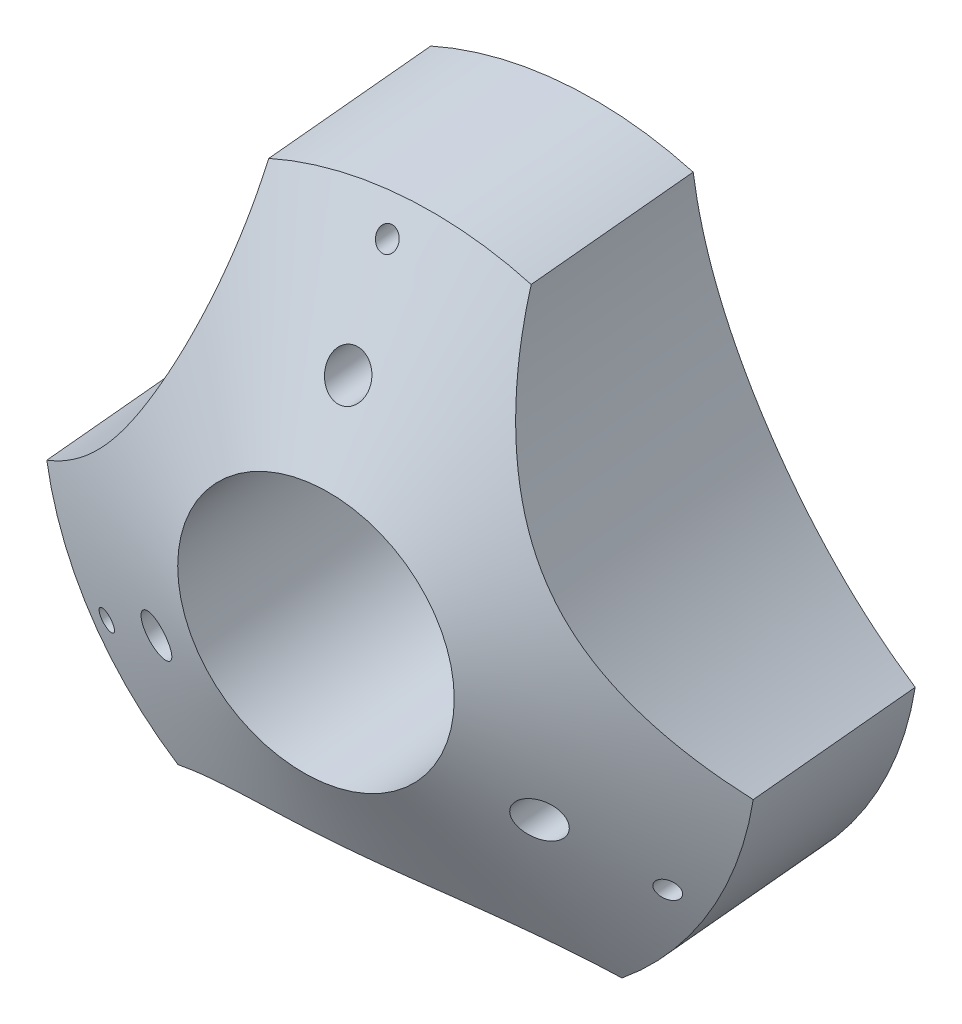
SolidWorks part; units mm, degrees
material "ABS"
ref_plane "前视基准面" through (0, 0, 0) normal (0, 0, 1) x (1, 0, 0)
ref_plane "上视基准面" through (0, 0, 0) normal (0, 1, 0) x (1, 0, 0)
ref_plane "右视基准面" through (0, 0, 0) normal (1, 0, 0) x (0, 0, -1)
other "Configuration Table"
sketch "草图1" plane through (0, 0, 0) normal (0, 1, 0) x (1, 0, 0)
  line L0 (0, 0) -> (50000, 0) construction
  line L1 (0, 0) -> (43301.2702, 25000) construction
  line L2 (0, 0) -> (25000, 43301.2702) construction
  line L3 (0, 0) -> (0, 50000) construction
  line L4 (0, 0) -> (-25000, 43301.2702) construction
  line L5 (0, 0) -> (-43301.2702, 25000) construction
  line L6 (-31.9455, 0) -> (-30.3426, -17.5183)
  line L7 (-30.3426, -17.5183) -> (-61.1307, -35.2938)
  line L8 (-61.1307, -35.2938) -> (-64.36, 0)
  line L9 (-64.36, 0) -> (-31.9455, 0)
  line L10 (-62.9002, -15.9548) -> (-52.9418, -15.0436) construction
  line L11 (-52.9418, -15.0436) -> (-54.3182, 0)
  line L12 (-52.9418, -15.0436) -> (-51.5928, -29.7871)
  spline S0 degree 4 poles (4.5441, -13.9852) (5.069, -13.9115) (6.1117, -13.7144) (7.5966, -13.2868) (9.4525, -12.4738) (11.1485, -11.4611) (12.673, -10.2854) (14.0902, -8.9027) (15.2006, -7.528) (16.0517, -6.2294) (16.6357, -5.1571) (16.9969, -4.4036) (17.2795, -3.7437) (17.4701, -3.2541) (17.647, -2.7595) (17.7869, -2.3315) (17.8956, -1.9726) (17.9965, -1.6106) (18.0724, -1.3201) (18.1431, -1.0312) (18.201, -0.7763) (18.2495, -0.5466) (18.2961, -0.3139) (18.338, -0.0934) (18.3688, 0.0809) (18.404, 0.2961) (18.438, 0.517) (18.4698, 0.7375) (18.5019, 0.9839) (18.5336, 1.2626) (18.5616, 1.5443) (18.5855, 1.8273) (18.6051, 2.1103) (18.6204, 2.3933) (18.6344, 2.7473) (18.6427, 3.1726) (18.6402, 3.6687) (18.606, 4.6606) (18.4743, 6.0736) (18.1443, 7.891) (17.4882, 10.0676) (16.5951, 12.1579) (15.4804, 14.1385) (14.1536, 15.9992) (12.6297, 17.7192) (10.7951, 19.3989) (8.6272, 20.9716) (6.1287, 22.3558) (3.3088, 23.4722) (0.3713, 24.2251) (-2.6362, 24.611) (-5.6679, 24.6319) (-8.6804, 24.2953) (-11.6337, 23.6131) (-14.4905, 22.6011) (-17.8988, 20.9477) (-21.6682, 18.3857) (-25.4815, 14.66) (-28.8831, 9.6089) (-31.2279, 3.9916) (-32.5355, -2.3024) (-32.5832, -9.4982) (-30.886, -17.2942) (-27.0418, -25.1548) (-21.1423, -32.1629) (-13.78, -37.6027) (-5.394, -41.2569) (3.5764, -43.0207) (12.7127, -42.8868) (21.6333, -40.9289) (30.0036, -37.2857) (37.5425, -32.1439) (44.0239, -25.7248) (49.277, -18.2707) (53.1837, -10.0336) (55.6748, -1.2666) (56.7255, 7.7843) (56.3496, 16.8863) (54.5948, 25.8236) (51.5367, 34.4007) (47.2736, 42.4454) (41.6252, 50.2164) (33.2939, 58.6988) (21.6024, 66.7973) (6.2316, 72.9489) (-11.9297, 75.3897) (-30.1426, 73.5037) (-47.4501, 67.5662) (-63.0493, 58.0235) (-76.3038, 45.4399) (-86.7456, 30.4509) (-94.067, 13.7235) (-98.1075, -4.0757) (-98.837, -22.3066) (-96.337, -40.374) (-90.7813, -57.7411) (-82.4178, -73.9383) (-71.5503, -88.568) (-58.5225, -101.306) (-43.7037, -111.9004) (-27.476, -120.169) (-10.2235, -125.9948) (7.6766, -129.3207) (25.8616, -130.1437) (43.989, -128.5088) (59.522, -125.003) (72.4202, -120.5917) (82.8104, -116.0253) (90.8771, -111.8583) (98.6697, -107.1992) (106.1617, -102.071) (114.2246, -95.801) (122.6763, -88.2215) (131.2888, -79.1727) (139.0767, -69.4058) (144.8157, -60.9536) (149.48, -53.1674) (153.2371, -46.1706) (156.1751, -40.0285) (158.8259, -33.7588) (160.8418, -28.4575) (162.3378, -24.1741) (163.5443, -20.3917) (164.5049, -17.1274) (165.2564, -14.393) (165.828, -12.1982) (166.3703, -9.9944) (166.8184, -8.0627) (167.1848, -6.398) (167.4765, -5.0161) (167.7053, -3.8925) (167.892, -2.9476) (168.0629, -2.0497) (168.1956, -1.3461) (168.4043, -0.1916) (168.4882, 0.2863) (168.6688, 1.3366) (168.7622, 1.9047) (168.8711, 2.5704) (169.0198, 3.5044) (169.1948, 4.6573) (169.389, 6.0027) (169.5701, 7.3351) (169.7422, 8.6768) (169.9433, 10.3507) (170.1641, 12.3645) (170.391, 14.7154) (170.6086, 17.4069) (170.7844, 20.1009) (170.9186, 22.7976) (171.0111, 25.4959) (171.0621, 28.1953) (171.0718, 30.8952) (171.0401, 33.595) (170.9491, 36.9686) (170.6302, 43.7113) (169.6923, 53.7988) (167.722, 65.8035) (165.138, 76.2991) (163.208, 82.7681) (162.3863, 85.3399) knots 0 0 0 0 0 0.002183 0.004365 0.006343 0.00832 0.010298 0.012275 0.014479 0.01558 0.016682 0.0173 0.017918 0.018536 0.018845 0.019463 0.019772 0.020081 0.02039 0.020699 0.021008 0.021162 0.021317 0.021626 0.021918 0.022064 0.02221 0.022501 0.022793 0.023085 0.023377 0.023669 0.023961 0.024253 0.024544 0.025128 0.025712 0.026296 0.028631 0.030966 0.033302 0.035637 0.037972 0.040307 0.042695 0.045083 0.048197 0.05131 0.054424 0.057538 0.060652 0.063766 0.066879 0.069993 0.073107 0.07622 0.082448 0.088676 0.094903 0.10113 0.107357 0.114993 0.124334 0.133675 0.143016 0.152357 0.161699 0.17104 0.18038 0.189722 0.199063 0.208404 0.217745 0.227086 0.236427 0.245769 0.25511 0.264451 0.273792 0.283133 0.292474 0.301815 0.313225 0.331907 0.35059 0.369272 0.387954 0.406636 0.425318 0.444001 0.462683 0.481365 0.500047 0.518729 0.537412 0.556094 0.574776 0.593458 0.612141 0.630823 0.649505 0.668187 0.68687 0.705552 0.724234 0.742916 0.752258 0.761599 0.77094 0.780281 0.789622 0.798963 0.812975 0.826987 0.840998 0.85034 0.85501 0.864351 0.873692 0.878363 0.883033 0.887704 0.892374 0.89471 0.897045 0.89938 0.901716 0.904051 0.905219 0.906387 0.907554 0.908722 0.909306 0.90989 0.911057 0.912447 0.912794 0.913142 0.913837 0.915226 0.916616 0.918006 0.919396 0.920785 0.922175 0.924955 0.927734 0.930513 0.933293 0.936072 0.938852 0.941631 0.944411 0.94719 0.94997 0.955529 0.972205 0.988882 1 1 1 1 1 construction
  spline S1 degree 4 poles (18.3541, 0) (18.3651, 0.0621) (18.381, 0.1554) (18.404, 0.2961) (18.438, 0.517) (18.4698, 0.7375) (18.5019, 0.9839) (18.5336, 1.2626) (18.5616, 1.5443) (18.5855, 1.8273) (18.6051, 2.1103) (18.6204, 2.3933) (18.6344, 2.7473) (18.6427, 3.1726) (18.6402, 3.6687) (18.606, 4.6606) (18.4743, 6.0736) (18.1443, 7.891) (17.4882, 10.0676) (16.5951, 12.1579) (15.4804, 14.1385) (14.1536, 15.9992) (12.6297, 17.7192) (10.7951, 19.3989) (8.6272, 20.9716) (6.1287, 22.3558) (3.3088, 23.4722) (0.3713, 24.2251) (-2.6362, 24.611) (-5.6679, 24.6319) (-8.6804, 24.2953) (-11.6337, 23.6131) (-14.4905, 22.6011) (-17.8988, 20.9477) (-21.6682, 18.3857) (-25.4815, 14.66) (-28.8831, 9.6089) (-31.2279, 3.9916) (-32.5355, -2.3024) (-32.5832, -9.4982) (-30.886, -17.2942) (-27.0418, -25.1548) (-21.1423, -32.1629) (-13.78, -37.6027) (-5.394, -41.2569) (3.5764, -43.0207) (12.7127, -42.8868) (21.6333, -40.9289) (30.0036, -37.2857) (37.5425, -32.1439) (44.0239, -25.7248) (49.277, -18.2707) (53.1837, -10.0336) (55.6748, -1.2666) (56.7255, 7.7843) (56.3496, 16.8863) (54.5948, 25.8236) (51.5367, 34.4007) (47.2736, 42.4454) (41.6252, 50.2164) (33.2939, 58.6988) (21.6024, 66.7973) (6.2316, 72.9489) (-11.9297, 75.3897) (-30.1426, 73.5037) (-47.4501, 67.5662) (-63.0493, 58.0235) (-76.3038, 45.4399) (-86.7456, 30.4509) (-94.067, 13.7235) (-98.1075, -4.0757) (-98.837, -22.3066) (-96.337, -40.374) (-90.7813, -57.7411) (-82.4178, -73.9383) (-71.5503, -88.568) (-58.5225, -101.306) (-43.7037, -111.9004) (-27.476, -120.169) (-10.2235, -125.9948) (7.6766, -129.3207) (25.8616, -130.1437) (43.989, -128.5088) (59.522, -125.003) (72.4202, -120.5917) (82.8104, -116.0253) (90.8771, -111.8583) (98.6697, -107.1992) (106.1617, -102.071) (114.2246, -95.801) (122.6763, -88.2215) (131.2888, -79.1727) (139.0767, -69.4058) (144.8157, -60.9536) (149.48, -53.1674) (153.2371, -46.1706) (156.1751, -40.0285) (158.8259, -33.7588) (160.8418, -28.4575) (162.3378, -24.1741) (163.5443, -20.3917) (164.5049, -17.1274) (165.2564, -14.393) (165.828, -12.1982) (166.3703, -9.9944) (166.8184, -8.0627) (167.1848, -6.398) (167.4765, -5.0161) (167.7053, -3.8925) (167.892, -2.9476) (168.0629, -2.0497) (168.1956, -1.3461) (168.3264, -0.6223) (168.3933, -0.2484) (168.4372, 0) knots 0.021626 0.021626 0.021626 0.021626 0.021626 0.021918 0.022064 0.02221 0.022501 0.022793 0.023085 0.023377 0.023669 0.023961 0.024253 0.024544 0.025128 0.025712 0.026296 0.028631 0.030966 0.033302 0.035637 0.037972 0.040307 0.042695 0.045083 0.048197 0.05131 0.054424 0.057538 0.060652 0.063766 0.066879 0.069993 0.073107 0.07622 0.082448 0.088676 0.094903 0.10113 0.107357 0.114993 0.124334 0.133675 0.143016 0.152357 0.161699 0.17104 0.18038 0.189722 0.199063 0.208404 0.217745 0.227086 0.236427 0.245769 0.25511 0.264451 0.273792 0.283133 0.292474 0.301815 0.313225 0.331907 0.35059 0.369272 0.387954 0.406636 0.425318 0.444001 0.462683 0.481365 0.500047 0.518729 0.537412 0.556094 0.574776 0.593458 0.612141 0.630823 0.649505 0.668187 0.68687 0.705552 0.724234 0.742916 0.752258 0.761599 0.77094 0.780281 0.789622 0.798963 0.812975 0.826987 0.840998 0.85034 0.85501 0.864351 0.873692 0.878363 0.883033 0.887704 0.892374 0.89471 0.897045 0.89938 0.901716 0.904051 0.905219 0.906387 0.907554 0.908722 0.909306 0.90989 0.911057 0.911057 0.911057 0.911057 0.911057
  spline S2 degree 4 poles (26.7771, -19.4547) (27.2791, -18.9699) (28.2564, -17.9726) (29.6389, -16.3972) (31.5138, -13.8737) (32.9647, -11.4834) (34.0651, -9.2998) (34.8847, -7.3726) (35.3191, -6.2309) (35.6599, -5.2409) (35.9229, -4.4091) (36.0959, -3.8235) (36.2363, -3.3192) (36.3702, -2.8132) (36.4765, -2.3905) (36.5777, -1.9654) (36.6735, -1.5395) (36.7371, -1.2443) (36.7899, -0.9895) (36.8338, -0.7701) (36.8689, -0.5895) (36.9122, -0.3614) (36.9643, -0.079) (37.0022, 0.137) (37.056, 0.4587) (37.1012, 0.7414) (37.1347, 0.96) (37.1737, 1.2255) (37.2176, 1.5413) (37.2661, 1.9157) (37.3168, 2.3441) (37.3624, 2.772) (37.4134, 3.3079) (37.4649, 3.9519) (37.524, 4.9191) (37.5642, 6.2107) (37.5499, 8.58) (37.2749, 12.0191) (36.4953, 16.2666) (34.9181, 21.2024) (32.7382, 25.9024) (30.2297, 29.9345) (27.5748, 33.3344) (24.3272, 36.7897) (20.4102, 40.1789) (15.3713, 43.5302) (9.113, 46.471) (2.4988, 48.4837) (-3.4771, 49.4179) (-8.6498, 49.6296) (-15.5371, 49.2939) (-22.3494, 48.0444) (-29.7217, 45.4984) (-37.3047, 41.3681) (-42.9225, 37.3494) (-49.2948, 31.5248) (-55.7813, 23.4083) (-61.4472, 12.6507) (-65.4181, -1.9048) (-66.0143, -20.496) (-61.2011, -38.6277) (-51.6663, -54.6681) (-39.5267, -67.0168) (-28.241, -75.0457) (-15.7631, -81.0448) (-2.4709, -84.9081) (11.2641, -86.5959) (25.0917, -86.1269) (38.6859, -83.5703) (51.7521, -79.0376) (62.4941, -73.4702) (71.067, -67.6625) (77.7289, -62.1925) (82.7475, -57.4634) (87.4361, -52.4071) (91.7776, -47.05) (95.7571, -41.4189) (99.3618, -35.5409) (102.1786, -30.2056) (104.3465, -25.5122) (105.8226, -21.9278) (106.7439, -19.5134) (107.4694, -17.486) (108.0246, -15.8552) (108.5543, -14.216) (109.0585, -12.5688) (109.5372, -10.914) (109.9904, -9.2519) (110.418, -7.5833) (110.7697, -6.1172) (111.0551, -4.8577) (111.2824, -3.8044) (111.4574, -2.9629) (111.6056, -2.2213) (111.7181, -1.6396) (111.7961, -1.2276) (111.8764, -0.7956) (111.9824, -0.2107) (112.0406, 0.1173) (112.149, 0.7476) (112.2197, 1.1704) (112.2736, 1.499) (112.3401, 1.912) (112.4454, 2.5814) (112.5829, 3.4978) (112.7468, 4.6683) (112.9181, 6.007) (113.1127, 7.6834) (113.3147, 9.6981) (113.5046, 12.0531) (113.6588, 14.7487) (113.7504, 17.4473) (113.7796, 20.1472) (113.7303, 24.197) (113.4243, 30.2662) (112.8255, 35.6383) (112.057, 40.3021) (111.5392, 42.9519) knots 0 0 0 0 0 0.005611 0.011222 0.016833 0.02525 0.028055 0.030861 0.033666 0.035069 0.036472 0.037875 0.038576 0.039277 0.04068 0.041381 0.042083 0.042784 0.043135 0.043486 0.043836 0.044187 0.044888 0.045754 0.046187 0.04662 0.047052 0.047485 0.048351 0.049216 0.050082 0.050948 0.051813 0.053545 0.055276 0.058738 0.062201 0.072588 0.082976 0.093363 0.103751 0.114138 0.121063 0.127988 0.141838 0.155688 0.169538 0.183388 0.197238 0.204163 0.211088 0.238788 0.252638 0.266488 0.280339 0.294189 0.321888 0.349589 0.377289 0.414571 0.469971 0.497671 0.525371 0.553071 0.580771 0.608471 0.636171 0.663871 0.691571 0.719271 0.746971 0.760821 0.774671 0.788521 0.802371 0.816222 0.830072 0.843922 0.857772 0.864697 0.871622 0.875084 0.878547 0.882009 0.885472 0.888934 0.892397 0.895859 0.899322 0.902784 0.904515 0.906247 0.907978 0.909709 0.910575 0.911008 0.91144 0.913172 0.914528 0.915207 0.915885 0.916563 0.917242 0.918599 0.921312 0.924025 0.926739 0.929452 0.934879 0.940306 0.945732 0.951159 0.956586 0.962013 0.978293 1 1 1 1 1 construction
  spline S3 degree 4 poles (36.9778, 0) (36.994, 0.0921) (37.0177, 0.2297) (37.056, 0.4587) (37.1012, 0.7414) (37.1347, 0.96) (37.1737, 1.2255) (37.2176, 1.5413) (37.2661, 1.9157) (37.3168, 2.3441) (37.3624, 2.772) (37.4134, 3.3079) (37.4649, 3.9519) (37.524, 4.9191) (37.5642, 6.2107) (37.5499, 8.58) (37.2749, 12.0191) (36.4953, 16.2666) (34.9181, 21.2024) (32.7382, 25.9024) (30.2297, 29.9345) (27.5748, 33.3344) (24.3272, 36.7897) (20.4102, 40.1789) (15.3713, 43.5302) (9.113, 46.471) (2.4988, 48.4837) (-3.4771, 49.4179) (-8.6498, 49.6296) (-15.5371, 49.2939) (-22.3494, 48.0444) (-29.7217, 45.4984) (-37.3047, 41.3681) (-42.9225, 37.3494) (-49.2948, 31.5248) (-55.7813, 23.4083) (-61.4472, 12.6507) (-65.4181, -1.9048) (-66.0143, -20.496) (-61.2011, -38.6277) (-51.6663, -54.6681) (-39.5267, -67.0168) (-28.241, -75.0457) (-15.7631, -81.0448) (-2.4709, -84.9081) (11.2641, -86.5959) (25.0917, -86.1269) (38.6859, -83.5703) (51.7521, -79.0376) (62.4941, -73.4702) (71.067, -67.6625) (77.7289, -62.1925) (82.7475, -57.4634) (87.4361, -52.4071) (91.7776, -47.05) (95.7571, -41.4189) (99.3618, -35.5409) (102.1786, -30.2056) (104.3465, -25.5122) (105.8226, -21.9278) (106.7439, -19.5134) (107.4694, -17.486) (108.0246, -15.8552) (108.5543, -14.216) (109.0585, -12.5688) (109.5372, -10.914) (109.9904, -9.2519) (110.418, -7.5833) (110.7697, -6.1172) (111.0551, -4.8577) (111.2824, -3.8044) (111.4574, -2.9629) (111.6056, -2.2213) (111.7181, -1.6396) (111.7961, -1.2276) (111.8764, -0.7956) (111.946, -0.4114) (111.9868, -0.1841) (112.0193, 0) knots 0.044888 0.044888 0.044888 0.044888 0.044888 0.045754 0.046187 0.04662 0.047052 0.047485 0.048351 0.049216 0.050082 0.050948 0.051813 0.053545 0.055276 0.058738 0.062201 0.072588 0.082976 0.093363 0.103751 0.114138 0.121063 0.127988 0.141838 0.155688 0.169538 0.183388 0.197238 0.204163 0.211088 0.238788 0.252638 0.266488 0.280339 0.294189 0.321888 0.349589 0.377289 0.414571 0.469971 0.497671 0.525371 0.553071 0.580771 0.608471 0.636171 0.663871 0.691571 0.719271 0.746971 0.760821 0.774671 0.788521 0.802371 0.816222 0.830072 0.843922 0.857772 0.864697 0.871622 0.875084 0.878547 0.882009 0.885472 0.888934 0.892397 0.895859 0.899322 0.902784 0.904515 0.906247 0.907978 0.909709 0.910575 0.911008 0.91144 0.913172 0.913172 0.913172 0.913172 0.913172
  dimension "D1" = 10
revolve "旋转1" add sketch "草图1" angle 360 about L8 region at (-43.2934, 0, 12.1792) region at (-31.6084, 0, 8.7737)
ref_plane "基准面1" through (-0.451, 0, -4.9287) normal (-0.0911, 0, -0.9958) x (-0.9958, 0, 0.0911)
sketch "草图2" plane through (-0.451, 0, -4.9287) normal (-0.0911, 0, -0.9958) x (-0.9958, 0, 0.0911)
  line L0 (64.0923, 32.2796) -> (64.0923, 29.2796) construction
  line L1 (64.0923, 0) -> (18.6326, 0) construction
  line L2 (64.0923, 0) -> (7.8006, 32.5) construction
  line L3 (64.0923, 0) -> (64.0923, 20) construction
  circle A0 centre (64.0923, 0) radius 32.2796 construction
  circle A1 centre (64.0923, 29.2796) radius 1
  circle A2 centre (7.8006, 32.5) radius 44.5
  circle A3 centre (120.3839, 32.5) radius 44.5
  circle A4 centre (89.4492, -14.6398) radius 1
  circle A5 centre (64.0923, -65) radius 44.5
  circle A6 centre (38.7354, -14.6398) radius 1
  circle A8 centre (64.0923, 20) radius 2
  circle A9 centre (81.4128, -10) radius 2
  circle A11 centre (46.7718, -10) radius 2
  circle A12 centre (64.0923, 0) radius 10.65
  dimension "D2" = 2
  dimension "D4" = 89
  dimension "D9" = 4
  dimension "D7" = 21.3
  dimension "D1" = 3
  dimension "D3" = 30
  dimension "D6" = 20
  dimension "D5" = 3
  dimension "D10" = 3
extrude "切除-拉伸1" cut sketch "草图2" against normal blind 63 contours A2 | A3 | A5 | A1 | A4 | A6 | L3 A8 | A8 L3 | A9 | A11 | A12 region at (-64.2766, 29.2796, 0.9112) region at (-8.2191, 32.5, -4.2179) region at (-120.3341, 32.5, 6.0403) region at (-89.5281, -14.6398, 3.2216) region at (-64.2766, -65, 0.9112) region at (-39.0252, -14.6398, -1.3993) region at (-64.2766, 20, 0.9112) region at (-81.5251, -10, 2.4894) region at (-47.0282, -10, -0.667) region at (-64.2766, 0, 0.9112)
fillet "圆角1" radius 3 1 edges at (-53.6655, 0, 0)
ref_plane "基准面2" through (2.2471, 0, 24.5597) normal (0.0911, 0, 0.9958) x (0.9958, 0, -0.0911)
ref_point "点1"
sketch "草图4" plane through (2.2471, 0, 24.5597) normal (0.0911, 0, 0.9958) x (0.9958, 0, -0.0911)
  circle A0 centre (-64.0923, 0) radius 12.5
  dimension "D1" = 25
extrude "切除-拉伸2" cut sketch "草图4" against normal blind 32
fillet "圆角2" radius 1.5 1 edges at (-51.7762, 0, 0.3455)
shell "抽壳1" thickness 2
